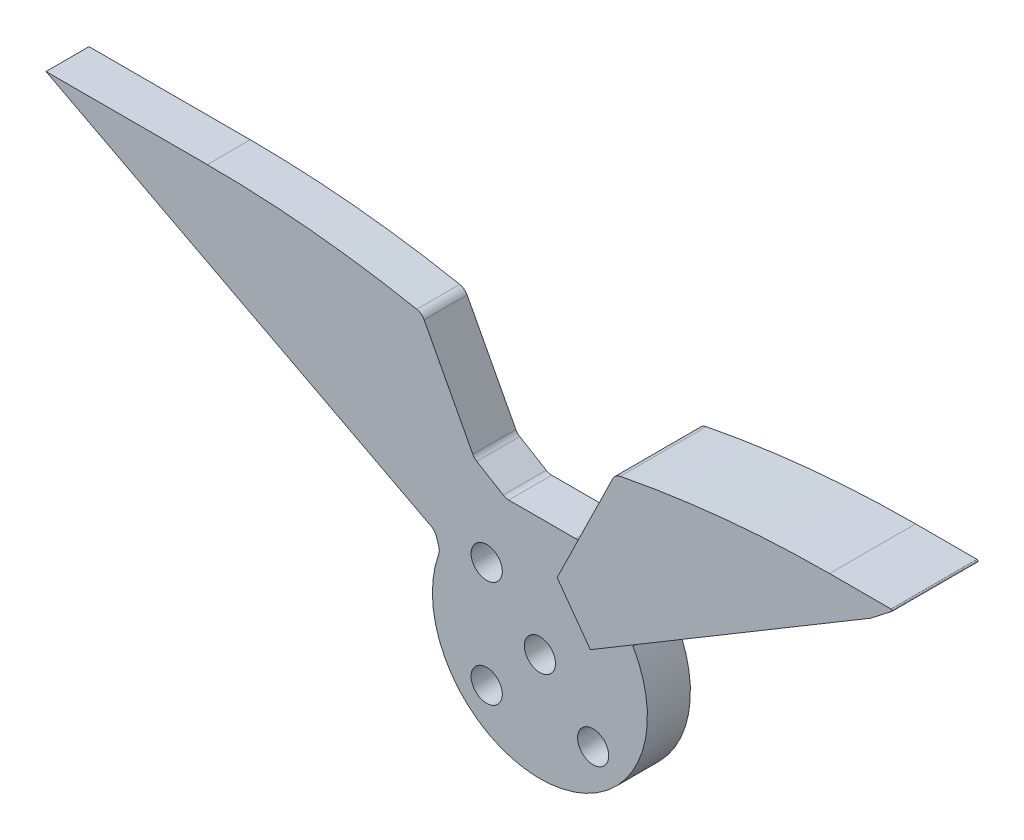
SolidWorks part; units mm, degrees
ref_plane "前视基准面" through (0, 0, 0) normal (0, 0, 1) x (1, 0, 0)
ref_plane "上视基准面" through (0, 0, 0) normal (0, 1, 0) x (1, 0, 0)
ref_plane "右视基准面" through (0, 0, 0) normal (1, 0, 0) x (0, 0, -1)
other "Configuration Table"
sketch "草图1" plane through (0, 0, 0) normal (0, 0, 1) x (1, 0, 0)
  circle A0 centre (0, 0) radius 10
  dimension "D1" = 20
extrude "凸台-拉伸1" add sketch "草图1" along normal blind 4
sketch "草图3" plane through (0, 0, 4) normal (0, 0, 1) x (1, 0, 0)
  line L0 (0, 11.0002) -> (0, 24) construction
  line L3 (-5.1769, 11.0002) -> (5.6008, 11.0002)
  line L5 (0, -10) -> (-57.8853, -10) construction
  line L8 (0, 0) -> (30.9406, 24)
  line L9 (30.9406, 24) -> (32.6019, 24) construction
  line L12 (-5.1769, 11.0002) -> (-10.9897, 22.0002)
  line L13 (5.6008, 11.0002) -> (10.9897, 22.0002)
  line L14 (-30.9406, 24) -> (-45.9406, 24)
  line L15 (-45.9406, 24) -> (0, 0)
  circle A1 centre (0, 0) radius 10 construction
  arc A3 (-30.9406, 24) -> (-10.9897, 22.0002) centre (-31.1526, -78.6357) cw
  arc A4 (30.9406, 24) -> (10.9897, 22.0002) centre (31.1526, -78.6357) ccw
  point P16 (-30.1505, 23.3871)
  point P17 (-29.9406, 23.9931)
  dimension "D1" = 1
  dimension "D2" = 52.2
  dimension "D3" = 1
  dimension "D4" = 26.1
  dimension "D5" = 24
  dimension "D6" = 15
extrude "凸台-拉伸3" add sketch "草图3" against normal blind 4
sketch "草图4" plane through (0, 0, 0) normal (0, 0, -1) x (-1, 0, 0)
  line L0 (0, 0) -> (-4.9497, 4.9497) construction
  line L1 (0, 0) -> (-4.9497, -4.9497) construction
  line L2 (0, 0) -> (4.9497, -4.9497) construction
  line L3 (0, 0) -> (4.9497, 4.9497) construction
  circle A0 centre (-4.9497, -4.9497) radius 1.45
  circle A1 centre (-4.9497, 4.9497) radius 1.45
  circle A2 centre (4.9497, 4.9497) radius 1.45
  circle A3 centre (4.9497, -4.9497) radius 1.45
  dimension "D5" = 2.9
  dimension "D1" = 7
  dimension "D2" = 7
  dimension "D3" = 7
  dimension "D4" = 7
extrude "切除-拉伸1" cut sketch "草图4" against normal blind 4
fillet "圆角5" radius 0.5 4 edges at (3.4997, -4.9497, 0) (-6.3997, -4.9497, 0) (-6.3997, 4.9497, 0) (3.4997, 4.9497, 0)
chamfer "倒角4" distance 1 angle 45 2 edges at (7.9016, 6.1291, 2) (-8.8634, 4.6304, 2)
sketch "草图5" plane through (0, 0, 4) normal (0, 0, 1) x (1, 0, 0)
  line L4 (10.9897, 22.0002) -> (5.6008, 11.0002) construction
  line L5 (8.6917, 6.742) -> (30.9406, 24) construction
  line L6 (10.9897, 22.0002) -> (5.6008, 11.0002)
  line L7 (8.6917, 6.742) -> (30.9406, 24)
  line L10 (5.6008, 11.0002) -> (8.6917, 6.742)
  arc A0 (30.9406, 24) -> (10.9897, 22.0002) centre (31.1526, -78.6357) ccw construction
  arc A1 (30.9406, 24) -> (10.9897, 22.0002) centre (31.1526, -78.6357) ccw
extrude "凸台-拉伸4" add sketch "草图5" along normal blind 4
chamfer "倒角5" distance 2 2 edges at (5.6008, 11.0002, 2) (-5.1769, 11.0002, 2)
chamfer "倒角6" distance 1 angle 45 2 edges at (6.0407, 11.8982, 4) (7.1463, 8.8711, 4)
fillet "圆角7" radius 1 4 edges at (6.4807, 12.7963, 2.5) (3.6008, 11.0002, 2) (-3.1769, 11.0002, 2) (-6.1113, 12.7685, 2)
fillet "圆角8" radius 1 2 edges at (-10.9897, 22.0002, 2) (10.9897, 22.0002, 4)
fillet "圆角9" radius 1 4 edges at (8.5045, 5.2605, 2) (8.6917, 6.742, 2.5) (-9.3028, 3.6686, 2) (-9.7497, 5.0934, 2)
sketch "草图6" plane through (0, 0, 0) normal (0, 0, -1) x (-1, 0, 0)
  circle A0 centre (0, 0) radius 1.45
  dimension "D1" = 2.9
extrude "切除-拉伸2" cut sketch "草图6" against normal blind 10
fillet "圆角10" radius 0.3 1 edges at (-1.45, 0, 0)
sketch "草图7" plane through (0, 0, 8) normal (0, 0, 1) x (1, 0, 0)
  line L0 (30.9406, 24) -> (36.9406, 24)
  line L1 (36.9406, 24) -> (34.7611, 22.3094)
  line L3 (8.6917, 6.742) -> (30.9406, 24) construction
  line L4 (30.9406, 24) -> (28.7611, 22.3094)
  line L5 (34.7611, 22.3094) -> (8.6917, 6.742)
  line L6 (8.6917, 6.742) -> (28.7611, 22.3094)
  dimension "D1" = 6
extrude "凸台-拉伸5" add sketch "草图7" against normal up to surface (8 mm away) up to face at (1.75, 0, 0)
fillet "圆角11" radius 0.1 1 edges at (36.9406, 24, 4)
